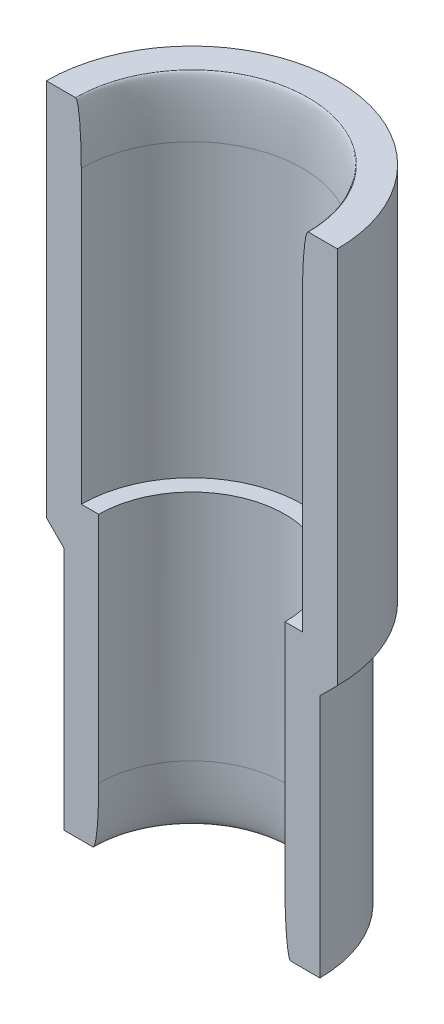
SolidWorks part; units mm, degrees
ref_plane "前视基准面" through (0, 0, 0) normal (0, 0, 1) x (1, 0, 0)
ref_plane "上视基准面" through (0, 0, 0) normal (0, 1, 0) x (1, 0, 0)
ref_plane "右视基准面" through (0, 0, 0) normal (1, 0, 0) x (0, 0, -1)
other "Configuration Table"
sketch "草图1" plane through (0, 0, 0) normal (0, 1, 0) x (1, 0, 0)
  circle A0 centre (0, 0) radius 8
  circle A1 centre (0, 0) radius 11
  dimension "D1" = 16
  dimension "D2" = 3
extrude "凸台-拉伸1" add sketch "草图1" along normal blind 25
sketch "草图2" plane through (0, 25, 0) normal (0, 1, 0) x (1, 0, 0)
  circle A0 centre (0, 0) radius 9.5
  circle A1 centre (0, 0) radius 12.5
  dimension "D1" = 19
  dimension "D2" = 3
extrude "凸台-拉伸2" add sketch "草图2" along normal blind 30
chamfer "倒角2" distance 4 angle 45 1 edges at (0, 25, 11)
fillet "圆角1" radius 5 1 edges at (0, 0, 8) second distance 0.5 first distance on face at (0, 25, 8)
fillet "圆角2" radius 0.5 1 edges at (0, 55, 9.5) second distance 5 first distance on face at (0, 55, 12.5)
sketch "草图3" plane through (0, 55, 0) normal (0, 1, 0) x (1, 0, 0)
  line L1 (-12.5, 0) -> (12.5, 0)
  line L2 (-12.5, 0) -> (-12.5, -12.5)
  line L3 (-12.5, -12.5) -> (12.5, -12.5)
  line L4 (12.5, 0) -> (12.5, -12.5)
  circle A0 centre (0, 0) radius 12.5 construction
extrude "切除-拉伸2" cut sketch "草图3" against normal through all
